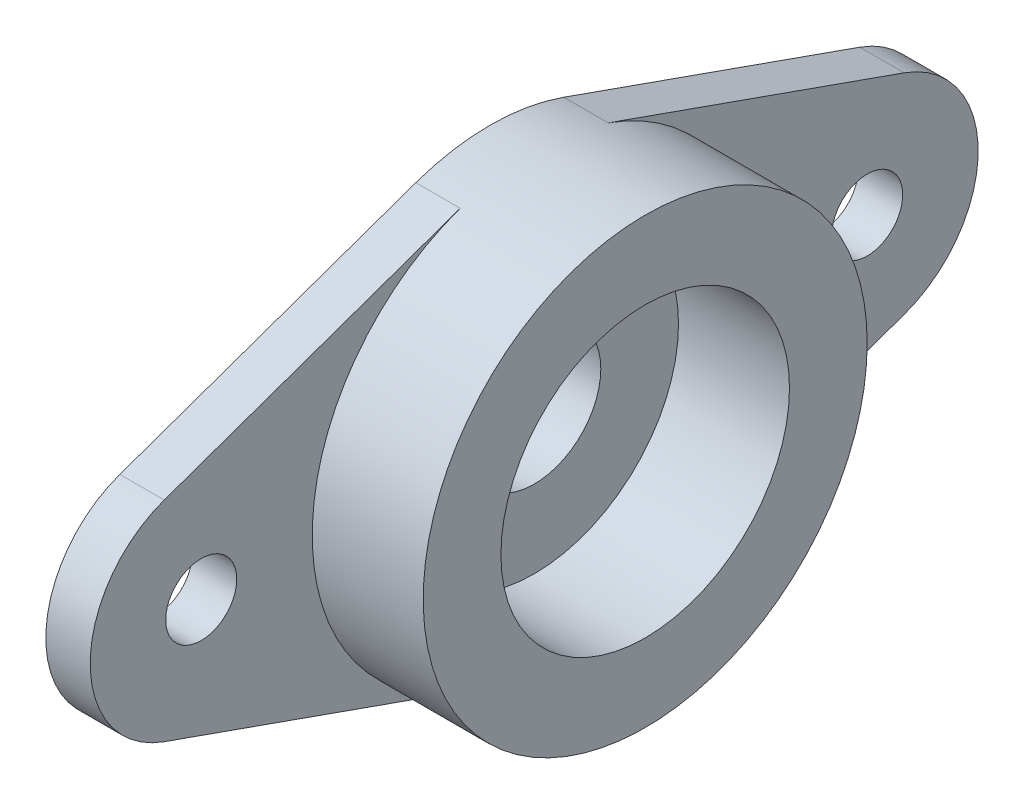
SolidWorks part; units mm, degrees
material "PLA (Orange)"
ref_plane "Front Plane" through (0, 0, 0) normal (0, 0, 1) x (1, 0, 0)
ref_plane "Top Plane" through (0, 0, 0) normal (0, 1, 0) x (1, 0, 0)
ref_plane "Right Plane" through (0, 0, 0) normal (1, 0, 0) x (0, 0, -1)
sketch "Sketch1" plane through (0, 0, 0) normal (1, 0, 0) x (0, 0, -1)
  line L0 (0, 0) -> (0, 7304.3141) construction
  line L1 (-16.6667, 4.714) -> (-3.3333, 9.4281)
  line L2 (-16.6667, -4.714) -> (-3.3333, -9.4281)
  line L3 (16.6667, -4.714) -> (3.3333, -9.4281)
  line L4 (16.6667, 4.714) -> (3.3333, 9.4281)
  circle A2 centre (0, 0) radius 6.5
  circle A3 centre (0, 0) radius 10
  arc A4 (-16.6667, -4.714) -> (-16.6667, 4.714) centre (-15, 0) cw
  circle A5 centre (-15, 0) radius 1.6
  circle A6 centre (15, 0) radius 1.6
  arc A7 (16.6667, -4.714) -> (16.6667, 4.714) centre (15, 0) ccw
  circle A8 centre (0, 0) radius 3
  dimension "D1" = 13
  dimension "D2" = 10
  dimension "D4" = 3.2
  dimension "D5" = 5
  dimension "D6" = 6
  dimension "D3" = 15
extrude "Boss-Extrude1" add sketch "Sketch1" along normal blind 2 contours A4 L2 A3 L1 A5 | L3 A7 L4 A3 A6 region at (0, 0, 13.2436) region at (0, 0, -13.2436)
extrude "Boss-Extrude2" add sketch "Sketch1<5>" along normal offset from surface (7 mm away) 5 contours L0 A3 A2 | A3 L0 A2 region at (0, 9.5772, -1.6432) up to face at (2, 0, 13.4) offset beyond the face yes
sketch "Sketch1<5>" plane through (0, 0, 0) normal (1, 0, 0) x (0, 0, -1) same geometry as "Sketch1"
extrude "Boss-Extrude3" add sketch "Sketch1<6>" along normal blind 2 contours L0 A2 A8 | A2 L0 A8 region at (0, 4.4662, -4.4662)
sketch "Sketch1<6>" plane through (0, 0, 0) normal (1, 0, 0) x (0, 0, -1) same geometry as "Sketch1"
